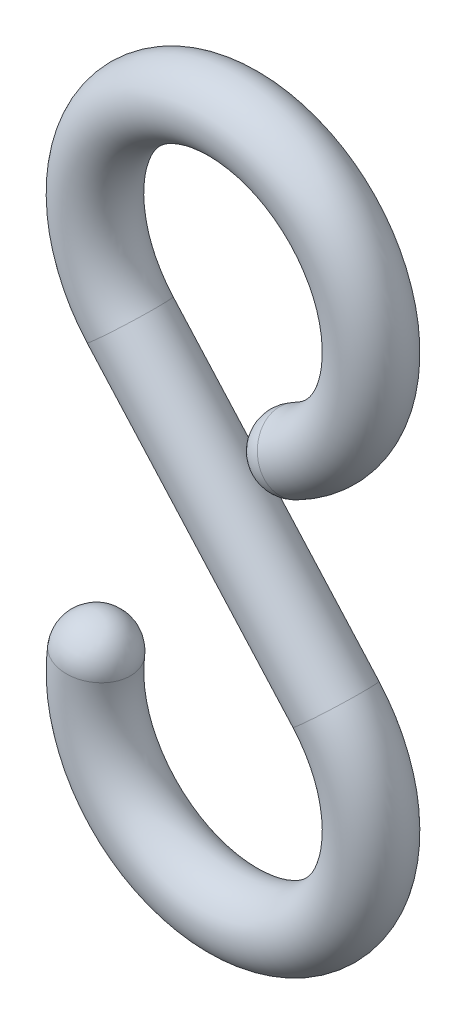
SolidWorks part; units mm, degrees
ref_plane "Front Plane" through (0, 0, 0) normal (0, 0, 1) x (1, 0, 0)
ref_plane "Top Plane" through (0, 0, 0) normal (0, 1, 0) x (1, 0, 0)
ref_plane "Right Plane" through (0, 0, 0) normal (1, 0, 0) x (0, 0, -1)
sketch "Sketch2" plane through (0, 0, 0) normal (0, 0, 1) x (1, 0, 0)
  line L0 (0, 0) -> (0, 38.1) construction
  line L1 (0, 19.05) -> (13.563, 19.05) construction
  line L2 (-9.466, 29.6333) -> (9.466, 8.4667)
  arc A0 (-12.5859, 1.6988) -> (9.466, 8.4667) centre (0, 0) ccw
  arc A1 (-9.466, 29.6333) -> (5.7198, 26.761) centre (0, 38.1) cw
  point P9 (5.7198, 26.761)
  dimension "D1" = 12.7
  dimension "D2" = 38.1
sweep "Sweep2" add path "Sketch2" circular profile diameter 6.35 parameters "D3"=6.35
dome "Dome1" faces to dome 1 distance 3.175 reverse direction no elliptical dome no face at (-15.7323, 2.1236, 0) parameters "D1"=3.175
dome "Dome3" faces to dome 1 distance 3.175 reverse direction no elliptical dome no face at (4.2899, 29.5957, 0) parameters "D1"=3.175
